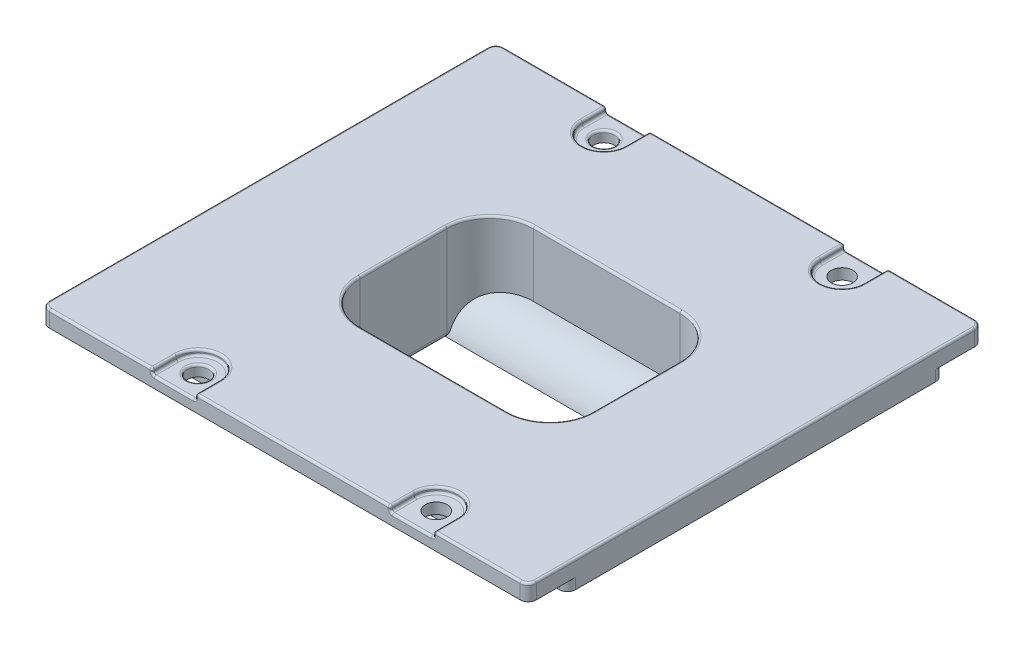
SolidWorks part; units mm, degrees
ref_plane "Front Plane" through (0, 0, 0) normal (0, 0, 1) x (1, 0, 0)
ref_plane "Top Plane" through (0, 0, 0) normal (0, 1, 0) x (1, 0, 0)
ref_plane "Right Plane" through (0, 0, 0) normal (1, 0, 0) x (0, 0, -1)
sketch "Sketch1" plane through (0, 0, 0) normal (0, 1, 0) x (1, 0, 0)
  line L0 (-43.5, 42) -> (-46.5, 42)
  line L1 (-43.5, 42) -> (43.5, 42)
  line L3 (-43.5, -42) -> (43.5, -42)
  line L4 (43.5, 42) -> (43.5, -42)
  line L5 (-43.5, 42) -> (43.5, -42) construction
  line L6 (-43.5, -42) -> (43.5, 42) construction
  line L7 (-46.5, 42) -> (-46.5, -42)
  line L8 (-46.5, -42) -> (-43.5, -42)
  circle A0 centre (-22, 37.5) radius 2
  circle A1 centre (-22, -37.5) radius 2
  circle A4 centre (22, 37.5) radius 2
  circle A5 centre (22, -37.5) radius 2
  point P0 (0, 0)
  dimension "D4" = 4
  dimension "D5" = 4
  dimension "D9" = 4
  dimension "D10" = 4
  dimension "D1" = 84
  dimension "D2" = 22
  dimension "D3" = 22
  dimension "D6" = 87
  dimension "D7" = 22
  dimension "D8" = 22
extrude "Boss-Extrude1" add sketch "Sketch1" along normal blind 3
sketch "Sketch2" plane through (0, 0, 0) normal (0, 1, 0) x (1, 0, 0)
  line L0 (43.5, -42) -> (43.5, 42) construction
  line L1 (-43.5, -34.75) -> (43.5, -34.75)
  line L2 (-43.5, -34.75) -> (-43.5, 34.75)
  line L3 (-43.5, 34.75) -> (43.5, 34.75)
  line L4 (43.5, -34.75) -> (43.5, 34.75)
  line L5 (-43.5, -34.75) -> (43.5, 34.75) construction
  line L6 (-43.5, 34.75) -> (43.5, -34.75) construction
  point P0 (0, 0)
  dimension "D1" = 69.5
extrude "Boss-Extrude2" add sketch "Sketch2" against normal blind 2
fillet "Fillet1" radius 1.5 8 edges at (43.5, 1.5, -42) (43.5, 1.5, 42) (43.5, -1, 34.75) (-43.5, -1, 34.75) (43.5, -1, -34.75) (-43.5, -1, -34.75) (-46.5, 1.5, 42) (-46.5, 1.5, -42)
sketch "Sketch3" plane through (0, 3, 0) normal (0, 1, 0) x (1, 0, 0)
  line L0 (-26, -37.5) -> (-26, -42)
  line L1 (-45, -42) -> (42, -42) construction
  line L2 (-26, -42) -> (-18, -42)
  line L3 (-18, -42) -> (-18, -37.5)
  line L4 (-26, 37.5) -> (-26, 44.4269)
  line L5 (-26, 44.4269) -> (-18, 44.4269)
  line L6 (-18, 44.4269) -> (-18, 37.5)
  line L7 (18, 37.5) -> (18, 46.5913)
  line L8 (18, 46.5913) -> (26, 46.5913)
  line L9 (26, 46.5913) -> (26, 37.5)
  line L10 (18, -37.5) -> (18, -43.8784)
  line L11 (18, -43.8784) -> (26, -43.8784)
  line L12 (26, -43.8784) -> (26, -37.5)
  arc A0 (-26, 37.5) -> (-18, 37.5) centre (-22, 37.5) ccw
  arc A1 (-18, -37.5) -> (-26, -37.5) centre (-22, -37.5) ccw
  arc A2 (18, 37.5) -> (26, 37.5) centre (22, 37.5) ccw
  arc A3 (26, -37.5) -> (18, -37.5) centre (22, -37.5) ccw
  point P18 (-26, 44.4269)
  point P25 (18, -43.8784)
  dimension "D1" = 8
  dimension "D2" = 8
  dimension "D3" = 8
  dimension "D4" = 8
extrude "Cut-Extrude1" cut sketch "Sketch3" against normal offset from surface (1 mm away) 2 up to face at (-0.75, 0, 0)
sketch "Sketch4" plane through (0, 3, 0) normal (0, 1, 0) x (1, 0, 0)
  line L1 (-21.55, 16) -> (21.55, 16)
  line L2 (-21.55, 16) -> (-21.55, -16)
  line L3 (-21.55, -16) -> (21.55, -16)
  line L4 (21.55, 16) -> (21.55, -16)
  line L5 (-21.55, 16) -> (21.55, -16) construction
  line L6 (-21.55, -16) -> (21.55, 16) construction
  point P0 (0, 0)
  dimension "D1" = 32
  dimension "D2" = 43.1
extrude "Cut-Extrude2" cut sketch "Sketch4" against normal through all
fillet "Fillet3" radius 8 4 edges at (-21.55, 0.5, -16) (-21.55, 0.5, 16) (21.55, 0.5, 16) (21.55, 0.5, -16)
fillet "Fillet2" radius 0.4 58 edges at (-22, 2, 42) (-22, 2, -42) (-26, 2, 39.75) (-18, 2, 39.75) (-18, 2, -39.75) (-26, 2, -39.75) (-18, 3, 39.75) (-26, 3, 39.75) (-26, 3, -39.75) (-22, 3, -33.5) (0, 3, 42) (34, 3, 42) (43.0607, 3, 41.5607) (43.5, 3, 0) (43.0607, 3, -41.5607) (-35.5, 3, 42) (-22, 2, 39.5) (-22, 2, 33.5) (-22, 2, -35.5) (-22, 2, -33.5) (-18, 2.5, -42) (-26, 2.5, -42) (-26, 2.5, 42) (-18, 2.5, 42) (-22, 3, 33.5) (-18, 3, -39.75) (0, 3, -42) (34, 3, -42) (-35.5, 3, -42) (18, 2.5, 42) (26, 2.5, 42) (26, 2.5, -42) (18, 2.5, -42) (18, 2, 39.75) (26, 2, 39.75) (26, 3, 39.75) (22, 3, 33.5) (26, 2, -39.75) (22, 2, -33.5) (26, 3, -39.75) (22, 3, -33.5) (22, 2, 33.5) (18, 3, 39.75) (22, 2, 42) (22, 2, -42) (18, 2, -39.75) (18, 3, -39.75) (19.2069, 3, -13.6569) (21.55, 3, 0) (19.2069, 3, 13.6569) (0, 3, 16) (-19.2069, 3, 13.6569) (-21.55, 3, 0) (-19.2069, 3, -13.6569) (0, 3, -16) (-46.0607, 3, 41.5607) (-46.5, 3, 0) (-46.0607, 3, -41.5607)
sketch "Sketch5" plane through (0, -2, 0) normal (0, -1, 0) x (1, 0, 0)
  line L8 (33.5, -24.75) -> (33.5, 24.75)
  line L9 (33.5, 24.75) -> (-33.5, 24.75)
  line L10 (-33.5, 24.75) -> (-33.5, -24.75)
  line L11 (-33.5, -24.75) -> (33.5, -24.75)
  line L12 (33.5, -24.75) -> (33.5, 24.75)
  line L13 (33.5, 24.75) -> (-33.5, 24.75)
  line L14 (-33.5, 24.75) -> (-33.5, -24.75)
  line L15 (-33.5, -24.75) -> (33.5, -24.75)
  line L24 (25.55, -8) -> (25.55, 8)
  line L25 (-13.55, -20) -> (13.55, -20)
  line L26 (-25.55, 8) -> (-25.55, -8)
  line L27 (13.55, 20) -> (-13.55, 20)
  line L28 (25.55, -8) -> (25.55, 8)
  line L29 (-13.55, -20) -> (13.55, -20)
  line L30 (-25.55, 8) -> (-25.55, -8)
  line L31 (13.55, 20) -> (-13.55, 20)
  line L36 (-21.55, 8) -> (-21.55, -8)
  line L37 (-13.55, -16) -> (13.55, -16)
  line L38 (21.55, -8) -> (21.55, 8)
  line L39 (13.55, 16) -> (-13.55, 16)
  line L40 (-21.55, 8) -> (-21.55, -8)
  line L41 (-13.55, -16) -> (13.55, -16)
  line L42 (21.55, -8) -> (21.55, 8)
  line L43 (13.55, 16) -> (-13.55, 16)
  arc A16 (25.55, 8) -> (13.55, 20) centre (13.55, 8) ccw
  arc A17 (13.55, -20) -> (25.55, -8) centre (13.55, -8) ccw
  arc A18 (-25.55, -8) -> (-13.55, -20) centre (-13.55, -8) ccw
  arc A19 (-13.55, 20) -> (-25.55, 8) centre (-13.55, 8) ccw
  arc A20 (25.55, 8) -> (13.55, 20) centre (13.55, 8) ccw
  arc A21 (13.55, -20) -> (25.55, -8) centre (13.55, -8) ccw
  arc A22 (-25.55, -8) -> (-13.55, -20) centre (-13.55, -8) ccw
  arc A23 (-13.55, 20) -> (-25.55, 8) centre (-13.55, 8) ccw
  arc A28 (-21.55, -8) -> (-13.55, -16) centre (-13.55, -8) ccw
  arc A29 (13.55, -16) -> (21.55, -8) centre (13.55, -8) ccw
  arc A30 (21.55, 8) -> (13.55, 16) centre (13.55, 8) ccw
  arc A31 (-13.55, 16) -> (-21.55, 8) centre (-13.55, 8) ccw
  arc A32 (-21.55, -8) -> (-13.55, -16) centre (-13.55, -8) ccw
  arc A33 (13.55, -16) -> (21.55, -8) centre (13.55, -8) ccw
  arc A34 (21.55, 8) -> (13.55, 16) centre (13.55, 8) ccw
  arc A35 (-13.55, 16) -> (-21.55, 8) centre (-13.55, 8) ccw
  line M21 (-13.55, 16) -> (13.55, 16)
  arc M22 (13.55, 16) -> (21.55, 8) centre (13.55, 8) cw
  line M23 (21.55, 8) -> (21.55, -8)
  arc M24 (21.55, -8) -> (13.55, -16) centre (13.55, -8) cw
  line M25 (13.55, -16) -> (-13.55, -16)
  arc M26 (-13.55, -16) -> (-21.55, -8) centre (-13.55, -8) cw
  line M27 (-21.55, -8) -> (-21.55, 8)
  arc M28 (-21.55, 8) -> (-13.55, 16) centre (-13.55, 8) cw
  dimension "D1" = 10
  dimension "D2" = 4
  dimension "D3" = 0
extrude "Boss-Extrude3" add sketch "Sketch5" along normal offset from surface (13 mm away) 18 contours L31 A23 L30 A22 L29 A21 L28 A20 M28 M21 M22 M23 M24 M25 M26 M27 up to face at (0, 3, 0)
sketch "Sketch7" plane through (-25.55, 0, 0) normal (-1, 0, 0) x (0, 0, 1)
  line L1 (-40.5, 3) -> (40.5, 3) construction
  line L2 (-16, -9) -> (-20, -9)
  line L3 (-20, -15) -> (-20, -2) construction
  line L5 (-20, -9) -> (-20, -15)
  line L6 (-20, -15) -> (-8.254, -15)
  arc A0 (-8.254, -15) -> (-16, -9) centre (-16, -17) ccw
  dimension "D3" = 16
  dimension "D1" = 20
  dimension "D2" = 16
extrude "Boss-Extrude4" add sketch "Sketch7" against normal up to surface (51.1 mm away) contours A0 L2 L5 L6 up to face at (25.55, -8.5, 0)
fillet "Fillet4" radius 12 2 edges at (25.55, -12, -20) (-25.55, -12, -20)
fillet "Fillet5" radius 1 19 edges at (-21.55, -15, 0) (-21.549, -15, -8.127) (21.55, -15, 0) (19.2069, -15, 13.6569) (0, -15, 16) (-19.2069, -15, 13.6569) (22.0353, -15, 16.4853) (25.55, -15, 0) (25.5493, -15, -8.127) (-25.55, -15, 0) (-22.0353, -15, 16.4853) (0, -15, 20) (-25.5493, -15, -8.127) (21.549, -15, -8.127) (-20.02, -9.71, -12.7052) (25.1502, -10.6983, -11.0717) (0, -15, -20) (-21.945, -15, -16.5746) (21.945, -15, -16.5746)
